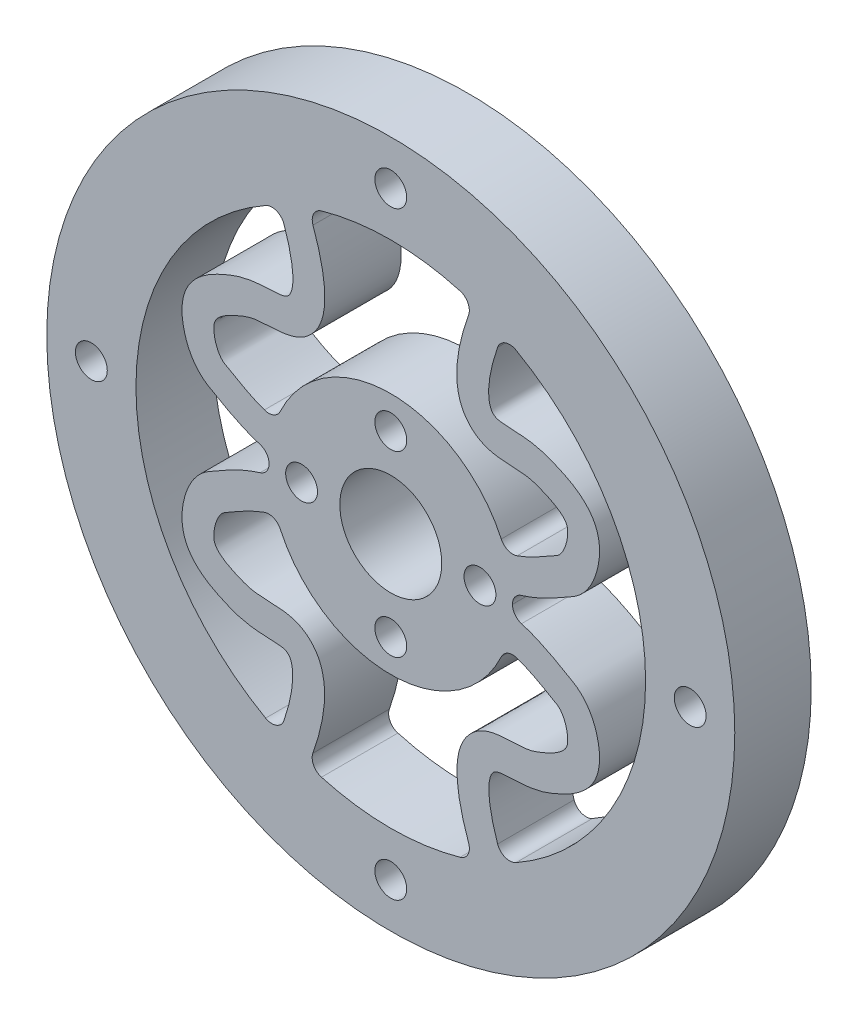
SolidWorks part; units mm, degrees
ref_plane "Front Plane" through (0, 0, 0) normal (0, 0, 1) x (1, 0, 0)
ref_plane "Top Plane" through (0, 0, 0) normal (0, 1, 0) x (1, 0, 0)
ref_plane "Right Plane" through (0, 0, 0) normal (1, 0, 0) x (0, 0, -1)
sketch "Sketch1" plane through (0, 0, 0) normal (0, 0, 1) x (1, 0, 0)
  line L0 (0, 0) -> (18.4664, 44.5819) construction
  line L1 (0, -55) -> (0, 55) construction
  line L2 (0, 0) -> (47.1742, 10.1563) construction
  line L3 (55, 0) -> (-55, 0) construction
  arc A1 (6.4819, 18.9205) -> (-6.4819, 18.9205) centre (0, 0) ccw
  circle A2 centre (0, 0) radius 23.5 construction
  circle A3 centre (0, 23.5) radius 1.25
  circle A4 centre (0, 0) radius 4
  circle A6 centre (0, 0) radius 7 construction
  circle A7 centre (0, 7) radius 1.25
  circle A8 centre (23.5, 0) radius 1.25
  circle A9 centre (0, -23.5) radius 1.25
  circle A10 centre (-23.5, 0) radius 1.25
  circle A11 centre (7, 0) radius 1.25
  circle A12 centre (0, -7) radius 1.25
  circle A13 centre (-7, 0) radius 1.25
  arc A16 (8.7932, -17.9633) -> (8.7932, 17.9633) centre (0, 0) ccw
  arc A17 (-8.7932, 17.9633) -> (-8.7935, -17.9631) centre (0, 0) ccw
  arc A18 (-6.4819, -18.9205) -> (6.4819, -18.9205) centre (0, 0) ccw
  arc A21 (8.9934, 3.2158) -> (-8.9934, 3.2158) centre (0, 0) ccw
  arc A22 (-8.9934, -3.2158) -> (8.9934, -3.2158) centre (0, 0) ccw
  arc A23 (-9.5199, 0.7706) -> (-9.5199, -0.7706) centre (0, 0) ccw
  arc A24 (9.5199, -0.7706) -> (9.5199, 0.7706) centre (0, 0) ccw
  arc A25 (-8.7932, 17.9633) -> (-8.7932, -17.9633) centre (0, 0) ccw
  arc A26 (-6.4819, -18.9205) -> (6.4819, -18.9205) centre (0, 0) ccw
  arc A27 (8.7932, -17.9633) -> (8.7932, 17.9633) centre (0, 0) ccw
  arc A28 (-6.4819, 18.9205) -> (6.4819, 18.9205) centre (0, 0) cw
  arc A29 (-6.4819, 18.9205) -> (6.4819, 18.9205) centre (0, 0) cw
  circle A30 centre (0, 0) radius 27
  spline S0 degree 3 poles (7.643, 18.4519) (5.7778, 13.9489) (5.1634, 10.9629) (10.3565, 10.5411) (13.312, 9.9538) (15.0291, 7.8952) (15.156, 5.9744) (14.756, 4.5155) (13.5132, 3.792) (10.8353, 2.3088) (9.2391, 1.9891) knots 0 0 0 0 0.431444 0.56367 0.601805 0.774668 0.810919 0.92807 0.948442 1 1 1 1 construction
  spline S1 degree 1 poles (6.4872, 18.9306) (8.9934, 3.2158) knots 0 0 1 1 construction
  spline S2 degree 3 poles (6.4872, 18.9306) (6.3547, 18.6106) (6.0873, 17.9528) (5.6292, 16.7563) (5.1722, 15.3834) (4.8588, 13.9093) (4.8388, 12.5136) (5.3348, 11.1343) (6.4315, 10.1275) (7.8279, 9.6057) (9.1158, 9.4061) (10.1537, 9.2645) (10.9448, 9.1459) (11.6215, 9.0134) (12.2675, 8.7446) (12.9889, 8.1775) (13.4978, 7.5289) (13.7569, 7.0583) (13.8361, 6.7906) (13.8532, 6.6406) (13.8539, 6.4034) (13.8067, 6.0097) (13.692, 5.6451) (13.5731, 5.4116) (13.4792, 5.276) (13.3998, 5.1942) (13.345, 5.1502) (13.2864, 5.11) (13.0828, 4.9915) (12.5911, 4.7146) (11.6615, 4.2117) (10.5158, 3.6854) (9.5955, 3.3615) (9.2024, 3.2576) (8.9934, 3.2158) knots 0 0 0 0 0.03125 0.0625 0.125 0.1875 0.25 0.3125 0.375 0.4375 0.5 0.53125 0.5625 0.59375 0.625 0.6875 0.71875 0.75 0.78125 0.796875 0.8125 0.84375 0.875 0.890625 0.90625 0.921875 0.929688 0.9375 0.945312 0.953125 0.96875 0.984375 0.992188 1 1 1 1 construction
  spline S3 degree 1 poles (8.7979, 17.9735) (9.4845, 0.7634) knots 0 0 1 1 construction
  spline S4 degree 3 poles (8.7979, 17.9735) (8.6706, 17.6662) (8.4118, 17.0295) (7.9832, 15.9096) (7.5798, 14.6889) (7.35, 13.5713) (7.375, 12.8533) (7.5011, 12.5763) (7.7072, 12.3564) (8.3685, 12.0615) (9.4534, 11.8833) (10.5036, 11.7415) (11.3277, 11.6161) (12.2663, 11.4472) (13.3266, 11.0174) (14.2013, 10.4246) (15.2112, 9.4792) (15.9439, 8.414) (16.3417, 7.1996) (16.3712, 6.3347) (16.2665, 5.5042) (16.0394, 4.745) (15.7383, 4.1449) (15.44, 3.7077) (15.0552, 3.2962) (14.5807, 2.9584) (14.0189, 2.6469) (12.7831, 1.9731) (11.2192, 1.2561) (10.0677, 0.8802) (9.4845, 0.7634) knots 0 0 0 0 0.03125 0.0625 0.125 0.1875 0.25 0.3125 0.375 0.4375 0.5 0.53125 0.5625 0.59375 0.625 0.65625 0.6875 0.75 0.78125 0.8125 0.84375 0.875 0.890625 0.90625 0.921875 0.9375 0.953125 0.96875 0.984375 1 1 1 1 only from (8.7979, 17.9735) to (9.5199, 0.7706) construction
  spline S5 degree 3 poles (8.7932, -17.9633) (8.79, -17.9554) (8.7567, -17.8738) (8.6749, -17.6687) (8.4734, -17.139) (8.1818, -16.282) (7.8736, -15.1267) (7.6883, -13.9814) (7.6869, -12.989) (7.8823, -12.3406) (8.1054, -12.102) (8.4271, -11.9365) (9.2557, -11.8739) (10.0618, -11.8471) (10.9804, -11.7812) (12.0377, -11.5491) (12.9013, -11.2006) (14.0542, -10.6818) (15.2312, -9.9254) (16.129, -8.6624) (16.4338, -7.4205) (16.362, -6.2674) (16.0691, -5.0818) (15.5969, -4.1354) (15.1067, -3.5367) (14.775, -3.2284) (14.4887, -3.0134) (14.2147, -2.8483) (13.8407, -2.6359) (12.933, -2.1019) (11.3836, -1.3227) (10.1553, -0.9016) (9.5228, -0.7712) (9.5199, -0.7706) knots 0.008787 0.008787 0.008787 0.008787 0.010978 0.03125 0.0625 0.125 0.1875 0.25 0.3125 0.375 0.4375 0.5 0.53125 0.5625 0.59375 0.625 0.65625 0.6875 0.75 0.78125 0.8125 0.84375 0.875 0.90625 0.921875 0.929688 0.9375 0.945312 0.953125 0.96875 0.984375 0.999645 0.999715 0.999715 0.999715 0.999715
  spline S6 degree 3 poles (6.4819, -18.9205) (6.4787, -18.9127) (6.4396, -18.8168) (6.3458, -18.5819) (6.1173, -17.981) (5.7882, -17.0144) (5.4283, -15.669) (5.1906, -14.2306) (5.1744, -12.7623) (5.5236, -11.2838) (6.4091, -10.1677) (7.4536, -9.6259) (8.3495, -9.4264) (9.1698, -9.3775) (9.9472, -9.3517) (10.6747, -9.2897) (11.2367, -9.1704) (11.9316, -8.8979) (12.6373, -8.5785) (13.2115, -8.2351) (13.6129, -7.884) (13.8128, -7.5717) (13.8966, -7.2836) (13.8794, -6.6433) (13.7304, -6.0617) (13.5518, -5.655) (13.3968, -5.3985) (13.2654, -5.2404) (13.1607, -5.1452) (13.102, -5.1001) (12.9798, -5.0237) (12.5781, -4.795) (11.725, -4.2932) (10.6014, -3.7319) (9.6529, -3.3784) (9.2199, -3.2612) (8.9934, -3.2158) knots 0.007767 0.007767 0.007767 0.007767 0.009703 0.03125 0.0625 0.125 0.1875 0.25 0.3125 0.375 0.4375 0.46875 0.5 0.53125 0.5625 0.59375 0.625 0.65625 0.6875 0.71875 0.75 0.78125 0.8125 0.84375 0.875 0.890625 0.90625 0.921875 0.929688 0.9375 0.945312 0.953125 0.96875 0.984375 0.992188 1 1 1 1
  spline S7 degree 3 poles (-6.4819, -18.9205) (-6.4787, -18.9127) (-6.4396, -18.8168) (-6.3458, -18.5819) (-6.1173, -17.981) (-5.7882, -17.0144) (-5.4283, -15.669) (-5.1906, -14.2306) (-5.1744, -12.7623) (-5.5236, -11.2838) (-6.4091, -10.1677) (-7.4536, -9.6259) (-8.3495, -9.4264) (-9.1698, -9.3775) (-9.9472, -9.3517) (-10.6747, -9.2897) (-11.2367, -9.1704) (-11.9316, -8.8979) (-12.6373, -8.5785) (-13.2115, -8.2351) (-13.6129, -7.884) (-13.8128, -7.5717) (-13.8966, -7.2836) (-13.8794, -6.6433) (-13.7304, -6.0617) (-13.5518, -5.655) (-13.3968, -5.3985) (-13.2654, -5.2404) (-13.1607, -5.1452) (-13.102, -5.1001) (-12.9798, -5.0237) (-12.5781, -4.795) (-11.725, -4.2932) (-10.6014, -3.7319) (-9.6529, -3.3784) (-9.2199, -3.2612) (-8.9934, -3.2158) knots 0.007767 0.007767 0.007767 0.007767 0.009703 0.03125 0.0625 0.125 0.1875 0.25 0.3125 0.375 0.4375 0.46875 0.5 0.53125 0.5625 0.59375 0.625 0.65625 0.6875 0.71875 0.75 0.78125 0.8125 0.84375 0.875 0.890625 0.90625 0.921875 0.929688 0.9375 0.945312 0.953125 0.96875 0.984375 0.992188 1 1 1 1
  spline S8 degree 3 poles (-8.7932, -17.9633) (-8.79, -17.9554) (-8.7567, -17.8738) (-8.6749, -17.6687) (-8.4734, -17.139) (-8.1818, -16.282) (-7.8736, -15.1267) (-7.6883, -13.9814) (-7.6869, -12.989) (-7.8823, -12.3406) (-8.1054, -12.102) (-8.4271, -11.9365) (-9.2557, -11.8739) (-10.0618, -11.8471) (-10.9804, -11.7812) (-12.0377, -11.5491) (-12.9013, -11.2006) (-14.0542, -10.6818) (-15.2312, -9.9254) (-16.129, -8.6624) (-16.4338, -7.4205) (-16.362, -6.2674) (-16.0691, -5.0818) (-15.5969, -4.1354) (-15.1067, -3.5367) (-14.775, -3.2284) (-14.4887, -3.0134) (-14.2147, -2.8483) (-13.8407, -2.6359) (-12.933, -2.1019) (-11.3836, -1.3227) (-10.1553, -0.9016) (-9.5228, -0.7712) (-9.5199, -0.7706) knots 0.008787 0.008787 0.008787 0.008787 0.010978 0.03125 0.0625 0.125 0.1875 0.25 0.3125 0.375 0.4375 0.5 0.53125 0.5625 0.59375 0.625 0.65625 0.6875 0.75 0.78125 0.8125 0.84375 0.875 0.90625 0.921875 0.929688 0.9375 0.945312 0.953125 0.96875 0.984375 0.999645 0.999715 0.999715 0.999715 0.999715
  spline S9 degree 3 poles (-8.7932, 17.9633) (-8.7918, 17.96) (-8.7505, 17.8596) (-8.6586, 17.6312) (-8.442, 17.0629) (-8.1498, 16.2049) (-7.8467, 15.0635) (-7.6692, 13.9418) (-7.6757, 12.9779) (-7.8715, 12.3563) (-8.0964, 12.1167) (-8.4371, 11.9458) (-9.2658, 11.8777) (-10.069, 11.8441) (-10.9828, 11.7717) (-12.032, 11.5373) (-12.8928, 11.1914) (-14.0456, 10.676) (-15.225, 9.9252) (-16.1274, 8.6633) (-16.4332, 7.4192) (-16.3609, 6.2667) (-16.0683, 5.0811) (-15.5961, 4.1346) (-15.1056, 3.5358) (-14.7738, 3.2275) (-14.4873, 3.0125) (-14.2133, 2.8475) (-13.8395, 2.6353) (-12.9322, 2.1014) (-11.3836, 1.3225) (-10.1553, 0.9015) (-9.5228, 0.7712) (-9.5199, 0.7706) knots 0.003712 0.003712 0.003712 0.003712 0.004635 0.03125 0.0625 0.125 0.1875 0.25 0.3125 0.375 0.4375 0.5 0.53125 0.5625 0.59375 0.625 0.65625 0.6875 0.75 0.78125 0.8125 0.84375 0.875 0.90625 0.921875 0.929688 0.9375 0.945312 0.953125 0.96875 0.984375 0.999645 0.999715 0.999715 0.999715 0.999715
  spline S10 degree 3 poles (-6.4819, 18.9205) (-6.4806, 18.9172) (-6.4336, 18.8031) (-6.3299, 18.5456) (-6.0863, 17.9063) (-5.7559, 16.937) (-5.3998, 15.601) (-5.1697, 14.1783) (-5.1637, 12.7268) (-5.5288, 11.2628) (-6.4216, 10.1688) (-7.4564, 9.6374) (-8.3431, 9.4363) (-9.159, 9.3813) (-9.9341, 9.349) (-10.6616, 9.282) (-11.2295, 9.159) (-11.9278, 8.8858) (-12.6357, 8.5676) (-13.2116, 8.226) (-13.6132, 7.877) (-13.8119, 7.5679) (-13.8952, 7.283) (-13.878, 6.6417) (-13.729, 6.0603) (-13.5506, 5.6539) (-13.3956, 5.3976) (-13.2643, 5.2397) (-13.1596, 5.1445) (-13.1009, 5.0994) (-12.9784, 5.0229) (-12.5765, 4.7941) (-11.7238, 4.2925) (-10.6009, 3.7315) (-9.6528, 3.3783) (-9.2199, 3.2611) (-8.9934, 3.2158) knots 0.003306 0.003306 0.003306 0.003306 0.004127 0.03125 0.0625 0.125 0.1875 0.25 0.3125 0.375 0.4375 0.46875 0.5 0.53125 0.5625 0.59375 0.625 0.65625 0.6875 0.71875 0.75 0.78125 0.8125 0.84375 0.875 0.890625 0.90625 0.921875 0.929688 0.9375 0.945312 0.953125 0.96875 0.984375 0.992188 1 1 1 1
  spline S11 degree 3 poles (8.7932, 17.9633) (8.7918, 17.96) (8.7505, 17.8596) (8.6586, 17.6312) (8.442, 17.0629) (8.1498, 16.2049) (7.8467, 15.0635) (7.6692, 13.9418) (7.6757, 12.9779) (7.8715, 12.3563) (8.0964, 12.1167) (8.4371, 11.9458) (9.2658, 11.8777) (10.069, 11.8441) (10.9828, 11.7717) (12.032, 11.5373) (12.8928, 11.1914) (14.0456, 10.676) (15.225, 9.9252) (16.1274, 8.6633) (16.4332, 7.4192) (16.3609, 6.2667) (16.0683, 5.0811) (15.5961, 4.1346) (15.1056, 3.5358) (14.7738, 3.2275) (14.4873, 3.0125) (14.2133, 2.8475) (13.8395, 2.6353) (12.9322, 2.1014) (11.3836, 1.3225) (10.1553, 0.9015) (9.5228, 0.7712) (9.5199, 0.7706) knots 0.003712 0.003712 0.003712 0.003712 0.004635 0.03125 0.0625 0.125 0.1875 0.25 0.3125 0.375 0.4375 0.5 0.53125 0.5625 0.59375 0.625 0.65625 0.6875 0.75 0.78125 0.8125 0.84375 0.875 0.90625 0.921875 0.929688 0.9375 0.945312 0.953125 0.96875 0.984375 0.999645 0.999715 0.999715 0.999715 0.999715
  spline S12 degree 3 poles (6.4819, 18.9205) (6.4806, 18.9172) (6.4336, 18.8031) (6.3299, 18.5456) (6.0863, 17.9063) (5.7559, 16.937) (5.3998, 15.601) (5.1697, 14.1783) (5.1637, 12.7268) (5.5288, 11.2628) (6.4216, 10.1688) (7.4564, 9.6374) (8.3431, 9.4363) (9.159, 9.3813) (9.9341, 9.349) (10.6616, 9.282) (11.2295, 9.159) (11.9278, 8.8858) (12.6357, 8.5676) (13.2116, 8.226) (13.6132, 7.877) (13.8119, 7.5679) (13.8952, 7.283) (13.878, 6.6417) (13.729, 6.0603) (13.5506, 5.6539) (13.3956, 5.3976) (13.2643, 5.2397) (13.1596, 5.1445) (13.1009, 5.0994) (12.9784, 5.0229) (12.5765, 4.7941) (11.7238, 4.2925) (10.6009, 3.7315) (9.6528, 3.3783) (9.2199, 3.2611) (8.9934, 3.2158) knots 0.003306 0.003306 0.003306 0.003306 0.004127 0.03125 0.0625 0.125 0.1875 0.25 0.3125 0.375 0.4375 0.46875 0.5 0.53125 0.5625 0.59375 0.625 0.65625 0.6875 0.71875 0.75 0.78125 0.8125 0.84375 0.875 0.890625 0.90625 0.921875 0.929688 0.9375 0.945312 0.953125 0.96875 0.984375 0.992188 1 1 1 1
  dimension "D2" = 40
  dimension "D3" = 54
  dimension "D4" = 2.5
  dimension "D5" = 8
  dimension "D8" = 2.5
  dimension "D11" = 22.5
  dimension "D12" = 55.35
  dimension "D9" = 4
  dimension "D10" = 4
extrude "Boss-Extrude1" add sketch "Sketch1" along normal blind 6 contours A30 A1 A13 A12 A11 A10 A9 A8 A7 A4 A3 A16 A18 A17 region at (-26.2363, 0, 0)
fillet "Fillet1" radius 1 16 edges at (-8.9934, 3.2158, 3) (9.5199, -0.7706, 3) (8.9934, -3.2158, 3) (-8.9934, -3.2158, 3) (-9.5199, 0.7706, 3) (-9.5199, -0.7706, 3) (6.4819, -18.9205, 3) (-8.7932, -17.9633, 3) (8.7932, -17.9633, 3) (-6.4819, -18.9205, 3) (-6.4819, 18.9205, 3) (-8.7932, 17.9633, 3) (9.5199, 0.7706, 3) (8.9934, 3.2158, 3) (8.7932, 17.9633, 3) (6.4819, 18.9205, 3)
ref_axis "Axis1" through (0, 0, 6) along (0, 0, -1)
